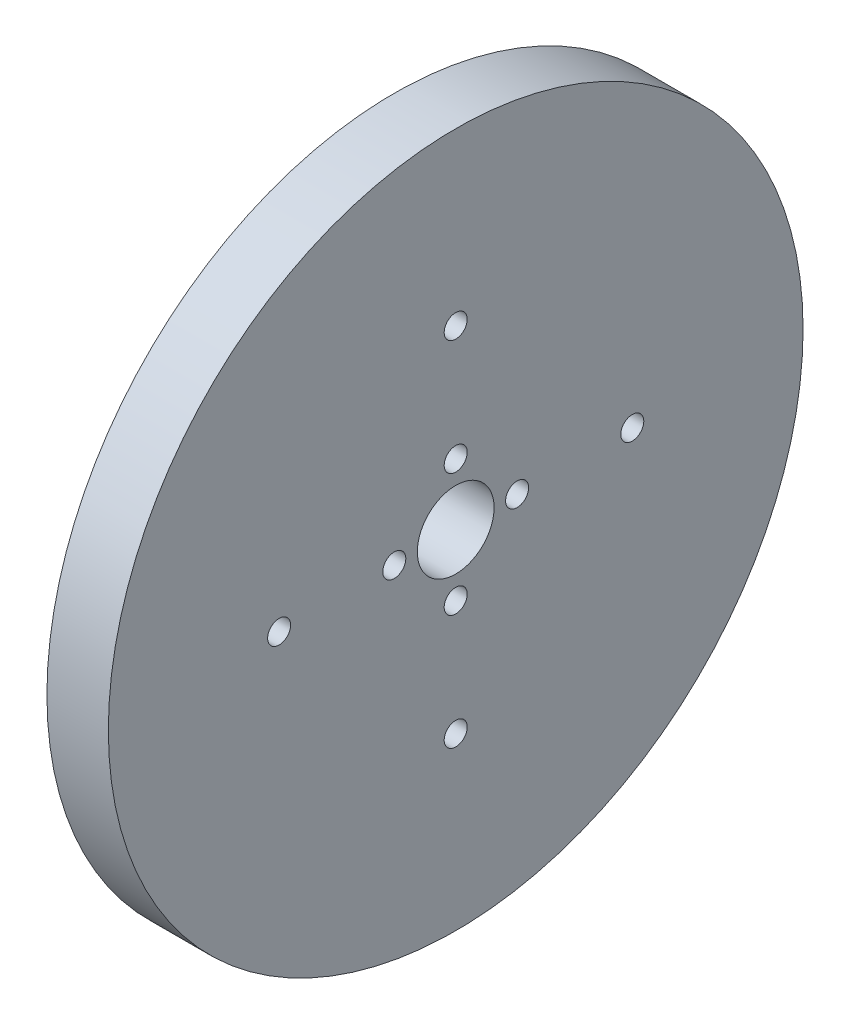
SolidWorks part; units mm, degrees
material "PMMA"
ref_plane "Front Plane" through (0, 0, 0) normal (0, 0, 1) x (1, 0, 0)
ref_plane "Top Plane" through (0, 0, 0) normal (0, 1, 0) x (1, 0, 0)
ref_plane "Right Plane" through (0, 0, 0) normal (1, 0, 0) x (0, 0, -1)
sketch "Sprocket" plane through (0, 0, 0) normal (1, 0, 0) x (0, 0, -1)
  circle A0 centre (0, 0) radius 45.25
  dimension "D1" = 90.5
extrude "Estrusione-Estrusione2" add sketch "Sprocket" along normal blind 8 contours A0
sketch "Schizzo1" plane through (0, 0, 0) normal (1, 0, 0) x (0, 0, -1)
  line L0 (0, 45.25) -> (0, -45.25) construction
  line L4 (-45.25, 0) -> (45.25, 0) construction
  circle A0 centre (0, 0) radius 5
  circle A1 centre (0, 23) radius 1.5
  circle A2 centre (8, 0) radius 1.5
  circle A3 centre (0, 8) radius 1.5
  circle A4 centre (23, 0) radius 1.5
  circle A5 centre (0, -8) radius 1.5
  circle A6 centre (0, -23) radius 1.5
  circle A7 centre (0, 0) radius 45.25 construction
  circle A8 centre (-8, 0) radius 1.5
  circle A9 centre (-23, 0) radius 1.5
  circle A10 centre (5.6569, 5.6569) radius 1.5 [skipped]
  circle A11 centre (-5.6569, 5.6569) radius 1.5 [skipped]
  circle A12 centre (-5.6569, -5.6569) radius 1.5 [skipped]
  circle A13 centre (5.6569, -5.6569) radius 1.5 [skipped]
  point P5 (0, 0)
  point P8 (0, 0)
  point P30 (0, 0)
  point P39 (0, 0)
  dimension "D1" = 10
  dimension "D2" = 3
  dimension "D5" = 3
  dimension "D3" = 8
  dimension "D6" = 15
  dimension "D4" = 8
  dimension "D7" = 4
extrude "Taglio-Estrusione2" cut sketch "Schizzo1" along direction (1, 0, 0) on the side of the normal through all
sketch "Schizzo2" plane through (0, 0, 0) normal (1, 0, 0) x (0, 0, -1)
  line L0 (0, 4) -> (0, 5) construction
  line L1 (3.9686, -0.5) -> (4.9749, -0.5)
  line L2 (-0.5, 4.9749) -> (-0.5, 3.9686)
  line L3 (0.5, 3.9686) -> (0.5, 4.9749)
  line L4 (4.9749, 0.5) -> (3.9686, 0.5)
  line L5 (-0.5, -3.9686) -> (-0.5, -4.9749)
  line L6 (0.5, -4.9749) -> (0.5, -3.9686)
  line L7 (-3.9686, 0.5) -> (-4.9749, 0.5)
  line L8 (-4.9749, -0.5) -> (-3.9686, -0.5)
  circle A0 centre (0, 0) radius 2
  circle A1 centre (0, 0) radius 4
  arc A3 (-0.5, 4.9749) -> (0.5, 4.9749) centre (0, 0) cw
  arc A4 (-0.5, 3.9686) -> (0.5, 3.9686) centre (0, 0) cw
  arc A5 (4.9749, 0.5) -> (4.9749, -0.5) centre (0, 0) cw
  arc A6 (3.9686, 0.5) -> (3.9686, -0.5) centre (0, 0) cw
  arc A7 (0.5, -4.9749) -> (-0.5, -4.9749) centre (0, 0) cw
  arc A8 (0.5, -3.9686) -> (-0.5, -3.9686) centre (0, 0) cw
  arc A9 (-4.9749, -0.5) -> (-4.9749, 0.5) centre (0, 0) cw
  arc A10 (-3.9686, -0.5) -> (-3.9686, 0.5) centre (0, 0) cw
  point P30 (0, 0)
  dimension "D1" = 4
  dimension "D2" = 8
  dimension "D3" = 0.5
  dimension "D5" = 4
  dimension "D4" = 0.5
extrude "Estrusione-Estrusione3" [suppressed] add sketch "Schizzo2" along normal blind 8 contours A1 A4 A0 | A9 L8 A1 L7 | A7 L6 A1 L5 | A5 L4 A1 L1 | L3 A3 L2 A4
equation "\"Thickness8\"=8"
equation "\"D1@Estrusione-Estrusione2\"=\"Thickness8\""
equation "\"D\"= 90.5"
equation "\"D1@Sprocket\"=\"D\""
equation "\"D4@Schizzo1\"=\"D3@Schizzo1\""
equation "\"D1@Estrusione-Estrusione3\"=\"Thickness8\""
